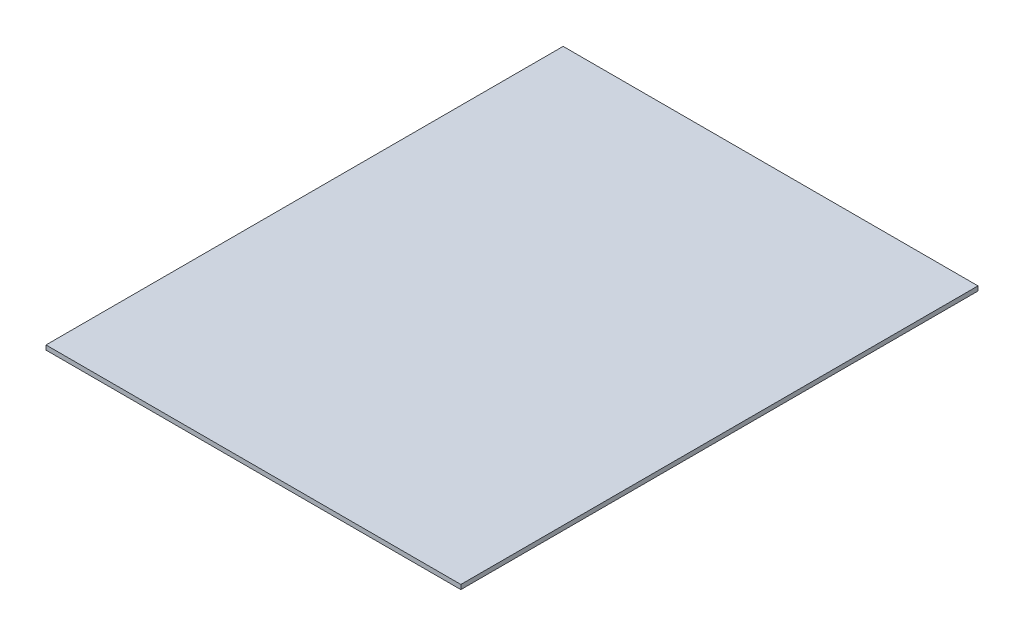
SolidWorks part; units mm, degrees
ref_plane "Front Plane" through (0, 0, 0) normal (0, 0, 1) x (1, 0, 0)
ref_plane "Top Plane" through (0, 0, 0) normal (0, 1, 0) x (1, 0, 0)
ref_plane "Right Plane" through (0, 0, 0) normal (1, 0, 0) x (0, 0, -1)
sketch "Sketch1" plane through (0, 0, 0) normal (0, 1, 0) x (1, 0, 0)
  line L1 (-292.8938, -365.125) -> (292.8938, -365.125)
  line L2 (-292.8938, -365.125) -> (-292.8938, 365.125)
  line L3 (-292.8938, 365.125) -> (292.8938, 365.125)
  line L4 (292.8938, -365.125) -> (292.8938, 365.125)
  line L5 (-292.8938, -365.125) -> (292.8938, 365.125) construction
  line L6 (-292.8938, 365.125) -> (292.8938, -365.125) construction
  point P0 (0, 0)
  dimension "D1" = 730.25
  dimension "D2" = 585.7875
extrude "Boss-Extrude1" add sketch "Sketch1" along normal blind 6.35
